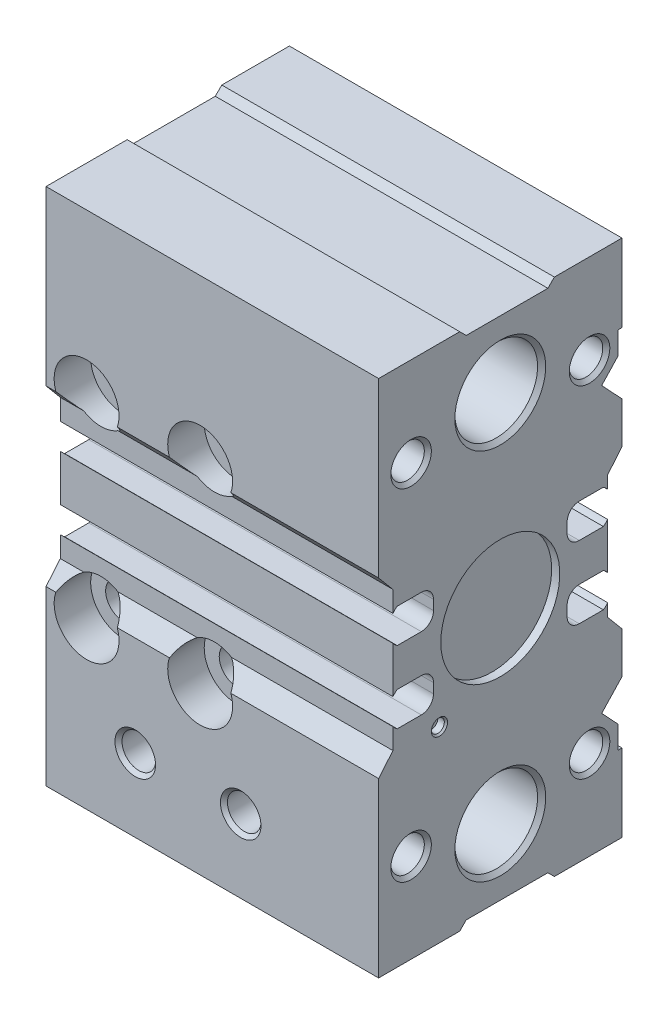
SolidWorks part; units mm, degrees
ref_plane "前视基准面" through (0, 0, 0) normal (0, 0, 1) x (1, 0, 0)
ref_plane "上视基准面" through (0, 0, 0) normal (0, 1, 0) x (1, 0, 0)
ref_plane "右视基准面" through (0, 0, 0) normal (1, 0, 0) x (0, 0, -1)
sketch "草图1" plane through (0, 0, 0) normal (1, 0, 0) x (0, 0, -1)
  line L0 (-15, -32) -> (-5, -32)
  line L1 (-5, -32) -> (-4.2, -31.2)
  line L2 (-4.2, -31.2) -> (5.8667, -31.2)
  line L3 (5.8667, -31.2) -> (6.6667, -32)
  line L4 (6.6667, -32) -> (15, -32)
  line L5 (15, -32) -> (15, -22.4348)
  line L6 (15, -22.4348) -> (14.5, -22.4348)
  line L7 (14.5, -22.4348) -> (14.5, -19.6333)
  line L8 (14.5, -19.6333) -> (12.5, -17.5)
  line L9 (12.5, -17.5) -> (15, -14.8333)
  line L10 (15, -14.8333) -> (15, -9.7142)
  line L11 (15, -9.7142) -> (13.2353, -7.6111)
  line L12 (13.2353, -7.6111) -> (13.2353, -6.0444)
  line L13 (12.7067, -6.5444) -> (9.7353, -6.5444)
  line L14 (8.2353, -5.0444) -> (8.2353, -3.8444)
  line L15 (9.7353, -2.3444) -> (12.7067, -2.3444)
  line L16 (13.2353, -2.8444) -> (13.2353, 2.8444)
  line L17 (12.7067, 2.3444) -> (9.7353, 2.3444)
  line L18 (8.2353, 3.8444) -> (8.2353, 5.0444)
  line L19 (9.7353, 6.5444) -> (12.7067, 6.5444)
  line L20 (13.2353, 6.0444) -> (13.2353, 7.6111)
  line L21 (13.2353, 7.6111) -> (15, 9.7142)
  line L22 (15, 9.7142) -> (15, 14.8333)
  line L23 (15, 14.8333) -> (12.5, 17.5)
  line L24 (12.5, 17.5) -> (14.5, 19.6333)
  line L25 (14.5, 19.6333) -> (14.5, 22.4348)
  line L26 (14.5, 22.4348) -> (15, 22.4348)
  line L27 (15, 22.4348) -> (15, 32)
  line L28 (15, 32) -> (6.6667, 32)
  line L29 (6.6667, 32) -> (5.8667, 31.2)
  line L30 (5.8667, 31.2) -> (-4.2, 31.2)
  line L31 (-4.2, 31.2) -> (-5, 32)
  line L32 (-5, 32) -> (-15, 32)
  line L33 (-15, 32) -> (-15, 10.7075)
  line L34 (-15, 10.7075) -> (-13.2353, 8.6044)
  line L35 (-13.2353, 8.6044) -> (-13.2353, 6.0444)
  line L36 (-12.7067, 6.5444) -> (-9.7353, 6.5444)
  line L37 (-8.2353, 5.0444) -> (-8.2353, 3.8444)
  line L38 (-9.7353, 2.3444) -> (-12.7067, 2.3444)
  line L39 (-13.2353, 2.8444) -> (-13.2353, -2.8444)
  line L40 (-12.7067, -2.3444) -> (-9.7353, -2.3444)
  line L41 (-8.2353, -3.8444) -> (-8.2353, -5.0444)
  line L42 (-9.7353, -6.5444) -> (-12.7067, -6.5444)
  line L43 (-13.2353, -6.0444) -> (-13.2353, -8.6044)
  line L44 (-13.2353, -8.6044) -> (-15, -10.7075)
  line L45 (-15, -10.7075) -> (-15, -32)
  arc A0 (13.2353, -6.0444) -> (12.7067, -6.5444) centre (11.221, -4.4444) cw
  arc A1 (9.7353, -6.5444) -> (8.2353, -5.0444) centre (9.7353, -5.0444) cw
  arc A2 (8.2353, -3.8444) -> (9.7353, -2.3444) centre (9.7353, -3.8444) cw
  arc A3 (12.7067, -2.3444) -> (13.2353, -2.8444) centre (11.221, -4.4444) cw
  arc A4 (13.2353, 2.8444) -> (12.7067, 2.3444) centre (11.221, 4.4444) cw
  arc A5 (9.7353, 2.3444) -> (8.2353, 3.8444) centre (9.7353, 3.8444) cw
  arc A6 (8.2353, 5.0444) -> (9.7353, 6.5444) centre (9.7353, 5.0444) cw
  arc A7 (12.7067, 6.5444) -> (13.2353, 6.0444) centre (11.221, 4.4444) cw
  arc A8 (-13.2353, 6.0444) -> (-12.7067, 6.5444) centre (-11.221, 4.4444) cw
  arc A9 (-9.7353, 6.5444) -> (-8.2353, 5.0444) centre (-9.7353, 5.0444) cw
  arc A10 (-8.2353, 3.8444) -> (-9.7353, 2.3444) centre (-9.7353, 3.8444) cw
  arc A11 (-12.7067, 2.3444) -> (-13.2353, 2.8444) centre (-11.221, 4.4444) cw
  arc A12 (-13.2353, -2.8444) -> (-12.7067, -2.3444) centre (-11.221, -4.4444) cw
  arc A13 (-9.7353, -2.3444) -> (-8.2353, -3.8444) centre (-9.7353, -3.8444) cw
  arc A14 (-8.2353, -5.0444) -> (-9.7353, -6.5444) centre (-9.7353, -5.0444) cw
  arc A15 (-12.7067, -6.5444) -> (-13.2353, -6.0444) centre (-11.221, -4.4444) cw
extrude "凸台-拉伸1" add sketch "草图1" along normal blind 41
sketch "草图2" plane through (0, 0, 0) normal (0, 0, 1) x (1, 0, 0)
  line L0 (0, 23) -> (0, 28.6)
  line L1 (0, 28.6) -> (0.5, 28.1)
  line L2 (0.5, 28.1) -> (40.5, 28.1)
  line L3 (40.5, 28.1) -> (41, 28.6)
  line L4 (41, 28.6) -> (41, 23)
  line L5 (41, 23) -> (0, 23)
  line L6 (41, 23) -> (0, 23) construction
revolve "切除-旋转1" cut sketch "草图2" angle 360 about L6 reverse direction yes
sketch "草图3" plane through (0, 0, 0) normal (0, 0, 1) x (1, 0, 0)
  line L0 (0, -23) -> (0, -17.4)
  line L1 (0, -17.4) -> (0.5, -17.9)
  line L2 (0.5, -17.9) -> (40.5, -17.9)
  line L3 (40.5, -17.9) -> (41, -17.4)
  line L4 (41, -17.4) -> (41, -23)
  line L5 (41, -23) -> (0, -23)
  line L6 (41, -23) -> (0, -23) construction
revolve "切除-旋转2" cut sketch "草图3" angle 360 about L6 reverse direction yes
ref_plane "基准面4" through (0, 12, 0) normal (0, 1, 0) x (1, 0, 0)
ref_plane "基准面5" through (0, 0, 15) normal (0, 0, 1) x (1, 0, 0)
sketch "草图4" plane through (0, 12, 0) normal (0, 1, 0) x (1, 0, 0)
  line L0 (19, 15) -> (21.5, 15)
  line L1 (21.5, 15) -> (21.067, 14.567)
  line L2 (21.067, 14.567) -> (21.067, 3.583)
  line L3 (21.067, 3.583) -> (21.15, 3.5)
  line L4 (21.15, 3.5) -> (21.15, -10.5)
  line L5 (21.15, -10.5) -> (23, -10.5)
  line L6 (23, -10.5) -> (23, -15)
  line L7 (23, -15) -> (19, -15)
  line L8 (19, -15) -> (19, 15)
  line L9 (19, -15) -> (19, 15) construction
revolve "切除-旋转3" cut sketch "草图4" angle 360 about L9 reverse direction yes
cosmetic thread "装饰螺纹线1" parameters "D1"=10, "D2"=5
sketch "草图5" plane through (0, 0, 0) normal (0, 0, 1) x (1, 0, 0)
  line L0 (19, 12) -> (-981, 12)
  line L1 (19, 12) -> (19, -988)
pattern_linear "阵列(线性)1" count 2 spacing 14 along (-1, 0, 0) count 2 spacing 24 along (0, -1, 0) of "切除-旋转3"
ref_plane "基准面6" through (0, 27, 0) normal (0, 1, 0) x (1, 0, 0)
sketch "草图6" plane through (0, 27, 0) normal (0, 1, 0) x (1, 0, 0)
  line L0 (11, 15) -> (13.5, 15)
  line L1 (13.5, 15) -> (13.067, 14.567)
  line L2 (13.067, 14.567) -> (13.067, 3.6934)
  line L3 (13.067, 3.6934) -> (11, 2.5)
  line L4 (11, 2.5) -> (11, 15)
  line L5 (11, 2.5) -> (11, 15) construction
revolve "切除-旋转4" cut sketch "草图6" angle 360 about L5 reverse direction yes
cosmetic thread "装饰螺纹线2" parameters "D1"=10, "D2"=5
ref_plane "基准面7" through (0, 0, -15) normal (0, 0, 1) x (1, 0, 0)
sketch "草图7" plane through (0, 0, 0) normal (0, 0, 1) x (1, 0, 0)
  line L0 (11, 27) -> (1011, 27)
  line L1 (11, 27) -> (11, -973)
pattern_linear "阵列(线性)2" count 2 spacing 17 along (1, 0, 0) count 2 spacing 54 along (0, -1, 0) of "切除-旋转4"
ref_plane "基准面8" through (0, -23, 0) normal (0, 1, 0) x (1, 0, 0)
sketch "草图8" plane through (0, -23, 0) normal (0, 1, 0) x (1, 0, 0)
  line L0 (11, -9.25) -> (13.067, -9.25)
  line L1 (13.067, -9.25) -> (13.067, -14.567)
  line L2 (13.067, -14.567) -> (13.5, -15)
  line L3 (13.5, -15) -> (11, -15)
  line L4 (11, -15) -> (11, -9.25)
  line L5 (11, -15) -> (11, -9.25) construction
revolve "切除-旋转5" cut sketch "草图8" angle 360 about L5 reverse direction yes
cosmetic thread "装饰螺纹线3" parameters "D1"=4.5, "D2"=5
sketch "草图9" plane through (0, -23, 0) normal (0, 1, 0) x (1, 0, 0)
  line L0 (24, -9.25) -> (26.067, -9.25)
  line L1 (26.067, -9.25) -> (26.067, -14.567)
  line L2 (26.067, -14.567) -> (26.5, -15)
  line L3 (26.5, -15) -> (24, -15)
  line L4 (24, -15) -> (24, -9.25)
  line L5 (24, -15) -> (24, -9.25) construction
revolve "切除-旋转6" cut sketch "草图9" angle 360 about L5 reverse direction yes
cosmetic thread "装饰螺纹线4" parameters "D1"=4.5, "D2"=5
sketch "草图10" plane through (0, 0, 0) normal (0, 1, 0) x (1, 0, 0)
  line L0 (0, 0) -> (0, 4.1)
  line L1 (0, 4.1) -> (10, 4.1)
  line L2 (10, 4.1) -> (10, 0)
  line L3 (10, 0) -> (0, 0)
  line L4 (10, 0) -> (0, 0) construction
revolve "切除-旋转7" cut sketch "草图10" angle 360 about L4 reverse direction yes
sketch "草图11" plane through (0, 0, 0) normal (0, 1, 0) x (1, 0, 0)
  line L0 (40, 0) -> (40, 7.3333)
  line L1 (40, 7.3333) -> (41, 7.3333)
  line L2 (41, 7.3333) -> (41, 0)
  line L3 (41, 0) -> (40, 0)
  line L4 (41, 0) -> (40, 0) construction
revolve "切除-旋转8" cut sketch "草图11" angle 360 about L4 reverse direction yes
ref_plane "基准面9" through (11, 0, 0) normal (1, 0, 0) x (0, 0, -1)
sketch "草图12" plane through (11, 0, 0) normal (1, 0, 0) x (0, 0, -1)
  line L0 (-10, -26.25) -> (-7.933, -26.25)
  line L1 (-7.933, -26.25) -> (-7.933, -31.567)
  line L2 (-7.933, -31.567) -> (-7.5, -32)
  line L3 (-7.5, -32) -> (-10, -32)
  line L4 (-10, -32) -> (-10, -26.25)
  line L5 (-10, -32) -> (-10, -26.25) construction
revolve "切除-旋转9" cut sketch "草图12" angle 360 about L5 reverse direction yes
cosmetic thread "装饰螺纹线5" parameters "D1"=4.5, "D2"=5
ref_plane "基准面10" through (24, 0, 0) normal (1, 0, 0) x (0, 0, -1)
sketch "草图13" plane through (24, 0, 0) normal (1, 0, 0) x (0, 0, -1)
  line L0 (-10, -26.25) -> (-7.933, -26.25)
  line L1 (-7.933, -26.25) -> (-7.933, -31.567)
  line L2 (-7.933, -31.567) -> (-7.5, -32)
  line L3 (-7.5, -32) -> (-10, -32)
  line L4 (-10, -32) -> (-10, -26.25)
  line L5 (-10, -32) -> (-10, -26.25) construction
revolve "切除-旋转10" cut sketch "草图13" angle 360 about L5 reverse direction yes
cosmetic thread "装饰螺纹线6" parameters "D1"=4.5, "D2"=5
ref_plane "基准面11" through (0, -8.9362, 0) normal (0, 1, 0) x (1, 0, 0)
sketch "草图14" plane through (0, -8.9362, 0) normal (0, 1, 0) x (1, 0, 0)
  line L0 (40, -7.5) -> (40, -6.7)
  line L1 (40, -6.7) -> (40.8, -6.7)
  line L2 (40.8, -6.7) -> (41, -6.5)
  line L3 (41, -6.5) -> (41, -7.5)
  line L4 (41, -7.5) -> (40, -7.5)
  line L5 (41, -7.5) -> (40, -7.5) construction
revolve "切除-旋转11" cut sketch "草图14" angle 360 about L5 reverse direction yes
ref_plane "基准面12" through (0, 21, 0) normal (0, 1, 0) x (1, 0, 0)
sketch "草图15" plane through (0, 21, 0) normal (0, 1, 0) x (1, 0, 0)
  line L0 (27.8, 11) -> (28.9934, 13.067)
  line L1 (28.9934, 13.067) -> (40.567, 13.067)
  line L2 (40.567, 13.067) -> (41, 13.5)
  line L3 (41, 13.5) -> (41, 11)
  line L4 (41, 11) -> (27.8, 11)
  line L5 (41, 11) -> (27.8, 11) construction
revolve "切除-旋转12" cut sketch "草图15" angle 360 about L5 reverse direction yes
cosmetic thread "装饰螺纹线7" parameters "D1"=11, "D2"=5
sketch "草图16" plane through (0, 21, 0) normal (0, 1, 0) x (1, 0, 0)
  line L0 (27.8, -11) -> (28.9934, -8.933)
  line L1 (28.9934, -8.933) -> (40.567, -8.933)
  line L2 (40.567, -8.933) -> (41, -8.5)
  line L3 (41, -8.5) -> (41, -11)
  line L4 (41, -11) -> (27.8, -11)
  line L5 (41, -11) -> (27.8, -11) construction
revolve "切除-旋转13" cut sketch "草图16" angle 360 about L5 reverse direction yes
cosmetic thread "装饰螺纹线8" parameters "D1"=11, "D2"=5
ref_plane "基准面13" through (0, -21, 0) normal (0, 1, 0) x (1, 0, 0)
sketch "草图17" plane through (0, -21, 0) normal (0, 1, 0) x (1, 0, 0)
  line L0 (27.8, 11) -> (28.9934, 13.067)
  line L1 (28.9934, 13.067) -> (40.567, 13.067)
  line L2 (40.567, 13.067) -> (41, 13.5)
  line L3 (41, 13.5) -> (41, 11)
  line L4 (41, 11) -> (27.8, 11)
  line L5 (41, 11) -> (27.8, 11) construction
revolve "切除-旋转14" cut sketch "草图17" angle 360 about L5 reverse direction yes
cosmetic thread "装饰螺纹线9" parameters "D1"=11, "D2"=5
sketch "草图18" plane through (0, -21, 0) normal (0, 1, 0) x (1, 0, 0)
  line L0 (27.8, -11) -> (28.9934, -8.933)
  line L1 (28.9934, -8.933) -> (40.567, -8.933)
  line L2 (40.567, -8.933) -> (41, -8.5)
  line L3 (41, -8.5) -> (41, -11)
  line L4 (41, -11) -> (27.8, -11)
  line L5 (41, -11) -> (27.8, -11) construction
revolve "切除-旋转15" cut sketch "草图18" angle 360 about L5 reverse direction yes
cosmetic thread "装饰螺纹线10" parameters "D1"=11, "D2"=5
ref_plane "B XY" through (0, 0, 0) normal (1, 0, 0) x (0, 0, -1)
ref_plane "B XZ" through (0, 0, 0) normal (0, -1, 0) x (-1, 0, 0)
ref_plane "B YZ" through (0, 0, 0) normal (0, 0, -1) x (-1, 0, 0)
ref_axis "B X" through (0, 0, 80.9) along (0, 0, -1)
ref_axis "B Y" through (0, -50, 0) along (0, 1, 0)
ref_axis "B Z" through (80.9, 0, 0) along (-1, 0, 0)
sketch3d "B"
  point P0 (0, 0, 0)
